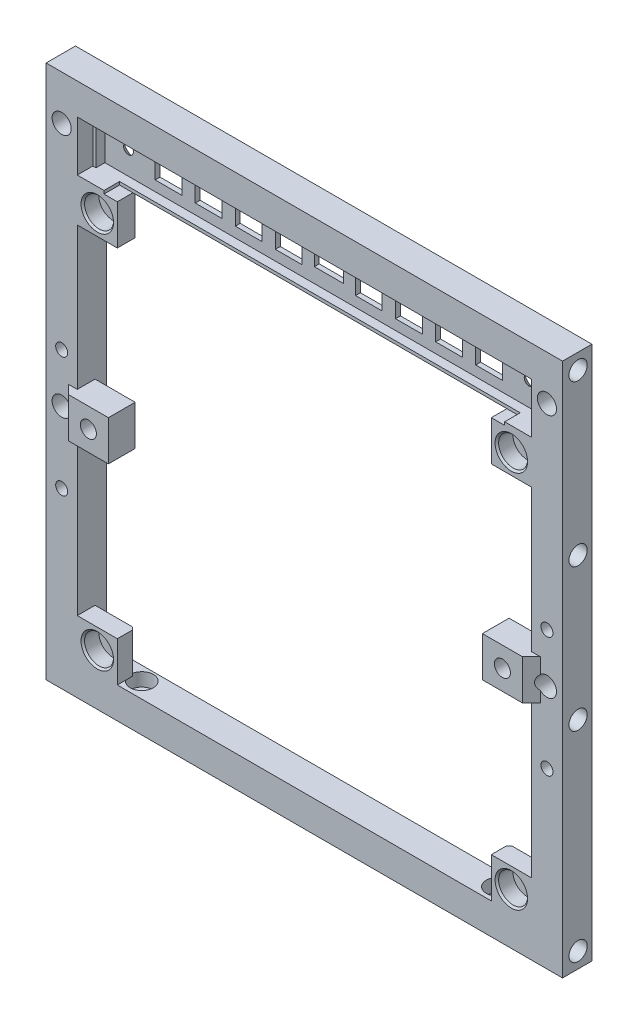
SolidWorks part; units mm, degrees
ref_plane "Front Plane" through (0, 0, 0) normal (0, 0, 1) x (1, 0, 0)
ref_plane "Top Plane" through (0, 0, 0) normal (0, 1, 0) x (1, 0, 0)
ref_plane "Right Plane" through (0, 0, 0) normal (1, 0, 0) x (0, 0, -1)
sketch "Sketch1" plane through (0, 0, 0) normal (0, 0, 1) x (1, 0, 0)
  line L1 (-58, -60) -> (58, -60)
  line L2 (-58, -60) -> (-58, 60)
  line L3 (-58, 60) -> (58, 60)
  line L4 (58, -60) -> (58, 60)
  line L5 (-58, -60) -> (58, 60) construction
  line L6 (-58, 60) -> (58, -60) construction
  line L7 (-51, -53) -> (51, -53)
  line L8 (-51, -53) -> (-51, 53)
  line L9 (-51, 53) -> (51, 53)
  line L10 (51, -53) -> (51, 53)
  line L11 (-51, -53) -> (51, 53) construction
  line L12 (-51, 53) -> (51, -53) construction
  point P0 (0, 0)
  point P6 (0, 0)
  dimension "D1" = 116
  dimension "D2" = 120
  dimension "D3" = 7
  dimension "D4" = 7
extrude "Boss-Extrude1" add sketch "Sketch1" along normal blind 7
sketch "Sketch2" plane through (-58, 0, 0) normal (-1, 0, 0) x (0, 0, 1)
  line L0 (3.5, 56.5) -> (3.5, -56.5) construction
  line L1 (7, 60) -> (0, 60) construction
  circle A0 centre (3.5, -56.5) radius 2.05
  circle A2 centre (3.5, 56.5) radius 2.05
  circle A3 centre (3.5, 20.5) radius 2.05
  circle A4 centre (3.5, -11.5) radius 2.05
  point P2 (3.5, 0)
  point P7 (3.5, 60)
  dimension "D2" = 4.1
  dimension "D3" = 36
  dimension "D4" = 45
  dimension "D1" = 3.5
extrude "Cut-Extrude1" cut sketch "Sketch2" against normal blind 6
mirror "Mirror1" about plane through (0, 0, 0) normal (1, 0, 0) of "Cut-Extrude1"
sketch "Sketch3" plane through (0, -53, 0) normal (0, 1, 0) x (1, 0, 0)
  line L0 (0, 0) -> (0, -7) construction
  line L1 (-51, 0) -> (51, 0) construction
  line L2 (-51, -7) -> (51, -7) construction
  line L3 (40, -3.5) -> (-40, -3.5) construction
  circle A0 centre (40, -3.5) radius 1.35
  circle A1 centre (-40, -3.5) radius 1.35
  point P9 (0, -3.5)
  dimension "D1" = 2.7
  dimension "D2" = 80
extrude "Cut-Extrude2" cut sketch "Sketch3" against normal through all
sketch "Sketch4" plane through (0, -53, 0) normal (0, 1, 0) x (1, 0, 0)
  circle A0 centre (40, -3.5) radius 2.6
  circle A1 centre (-40, -3.5) radius 2.6
  dimension "D1" = 5.2
extrude "Cut-Extrude3" cut sketch "Sketch4" against normal blind 3
sketch "Sketch5" plane through (0, 0, 0) normal (0, 0, -1) x (-1, 0, 0)
  line L0 (-54.5, -60) -> (-54.5, 60) construction
  line L1 (58, -60) -> (-58, -60) construction
  line L2 (-58, 60) -> (58, 60) construction
  line L3 (-51, 0) -> (-58, 0) construction
  line L4 (-51, -53) -> (-51, 53) construction
  line L5 (-58, -60) -> (-58, 60) construction
  line L6 (0, 60) -> (0, -60) construction
  line L7 (51, -53) -> (-51, -53) construction
  circle A0 centre (-54.5, 6) radius 1.35
  circle A1 centre (54.5, 6) radius 1.35
  circle A2 centre (-54.5, -21) radius 1.35
  circle A3 centre (54.5, -21) radius 1.35
  point P12 (-54.5, 0)
  point P13 (-54.5, 0)
  dimension "D1" = 2.7
  dimension "D2" = 6
  dimension "D3" = 32
extrude "Cut-Extrude4" cut sketch "Sketch5" against normal through all
sketch "Sketch6" plane through (0, 0, 0) normal (0, 0, -1) x (-1, 0, 0)
  circle A0 centre (-54.5, 6) radius 2.5
  circle A1 centre (54.5, 6) radius 2.5
  circle A2 centre (-54.5, -21) radius 2.5
  circle A3 centre (54.5, -21) radius 2.5
  dimension "D1" = 5
extrude "Cut-Extrude5" cut sketch "Sketch6" against normal blind 3
sketch "Sketch7" plane through (0, 0, 0) normal (0, 0, -1) x (-1, 0, 0)
  line L0 (-51, 53) -> (-58, 53) construction
  line L1 (-58, -60) -> (-58, 60) construction
  line L2 (-54.5, 50) -> (-54.5, -5) construction
  line L3 (-58, 60) -> (58, 60) construction
  circle A0 centre (-54.5, 50) radius 2.15
  circle A1 centre (-54.5, -5) radius 2.15
  point P8 (-54.5, 53)
  dimension "D1" = 4.3
  dimension "D2" = 10
  dimension "D3" = 55
extrude "Cut-Extrude6" cut sketch "Sketch7" against normal through all
mirror "Mirror2" about plane through (0, 0, 0) normal (1, 0, 0) of "Cut-Extrude6"
sketch "Sketch8" plane through (0, 0, 3) normal (0, 0, -1) x (-1, 0, 0)
  line L2 (-55.85, 3.8958) -> (-55.85, 8.1042)
  line L4 (-53.15, 3.8958) -> (-53.15, 8.1042)
  line L5 (-55.85, 3.8958) -> (-53.15, 8.1042) construction
  line L6 (-55.85, 8.1042) -> (-53.15, 3.8958) construction
  line L8 (-55.85, -23.1042) -> (-55.85, -18.8958)
  line L10 (-53.15, -23.1042) -> (-53.15, -18.8958)
  line L11 (-55.85, -23.1042) -> (-53.15, -18.8958) construction
  line L12 (-55.85, -18.8958) -> (-53.15, -23.1042) construction
  circle A0 centre (-54.5, 6) radius 2.5 construction
  circle A1 centre (-54.5, -21) radius 2.5 construction
  circle A2 centre (-54.5, -21) radius 2.5 construction
  arc A3 (-53.15, 8.1042) -> (-55.85, 8.1042) centre (-54.5, 6) ccw
  arc A4 (-53.15, -18.8958) -> (-55.85, -18.8958) centre (-54.5, -21) ccw
  circle A5 centre (-54.5, 6) radius 1.35 construction
  circle A6 centre (-54.5, -21) radius 1.35 construction
  arc A7 (-55.85, -23.1042) -> (-53.15, -23.1042) centre (-54.5, -21) ccw
  arc A8 (-55.85, 3.8958) -> (-53.15, 3.8958) centre (-54.5, 6) ccw
  point P0 (-54.5, 6)
  point P8 (-54.5, -21)
extrude "Cut-Extrude7" cut sketch "Sketch8" against normal blind 0.2
sketch "Sketch9" plane through (0, 0, 3.2) normal (0, 0, -1) x (-1, 0, 0)
  line L0 (-53.15, 6) -> (-53.15, 8.1042) construction
  line L1 (-55.85, 4.65) -> (-53.15, 4.65)
  line L2 (-55.85, 4.65) -> (-55.85, 7.35)
  line L3 (-55.85, 7.35) -> (-53.15, 7.35)
  line L4 (-53.15, 4.65) -> (-53.15, 7.35)
  line L5 (-55.85, 4.65) -> (-53.15, 7.35) construction
  line L6 (-55.85, 7.35) -> (-53.15, 4.65) construction
  line L7 (-53.15, -23.1042) -> (-53.15, -18.8958) construction
  line L8 (-55.85, -22.35) -> (-53.15, -22.35)
  line L9 (-55.85, -22.35) -> (-55.85, -19.65)
  line L10 (-55.85, -19.65) -> (-53.15, -19.65)
  line L11 (-53.15, -22.35) -> (-53.15, -19.65)
  line L12 (-55.85, -22.35) -> (-53.15, -19.65) construction
  line L13 (-55.85, -19.65) -> (-53.15, -22.35) construction
  arc A0 (-53.15, 6) -> (-55.85, 6) centre (-54.5, 6) ccw construction
  point P0 (-54.5, 6)
  point P8 (-54.5, -21)
extrude "Cut-Extrude8" cut sketch "Sketch9" against normal blind 0.2
mirror "Mirror3" about plane through (0, 0, 0) normal (1, 0, 0) of "Cut-Extrude8", "Cut-Extrude7"
sketch "Sketch10" plane through (0, 0, 7) normal (0, 0, 1) x (1, 0, 0)
  line L0 (51, -53) -> (51, 53) construction
  line L1 (51, -53) -> (45, -53)
  line L2 (51, -53) -> (51, -47)
  line L3 (51, -47) -> (45, -47)
  line L4 (45, -53) -> (45, -47)
  line L5 (51, -23.5) -> (45, -23.5)
  line L6 (51, -23.5) -> (51, -17.5)
  line L7 (51, -17.5) -> (45, -17.5)
  line L8 (45, -23.5) -> (45, -17.5)
  line L9 (-51, -53) -> (51, -53) construction
  dimension "D1" = 6
  dimension "D2" = 35.5
extrude "Boss-Extrude2" add sketch "Sketch10" against normal offset from surface (5.5 mm away) 1.5 up to face at (-52.35, -5, 0)
sketch "Sketch11" plane through (0, 0, 1.5) normal (0, 0, -1) x (-1, 0, 0)
  line L0 (-51, -23.5) -> (-45, -17.5) construction
  line L2 (-51, -53) -> (-45, -47) construction
  circle A0 centre (-48, -20.5) radius 1.65
  circle A1 centre (-48, -50) radius 1.65
  dimension "D1" = 3.3
extrude "Cut-Extrude9" cut sketch "Sketch11" against normal through all
mirror "Mirror4" about plane through (0, 0, 0) normal (1, 0, 0) of "Cut-Extrude9", "Boss-Extrude2"
sketch "Sketch12" plane through (0, 0, 0) normal (0, 0, -1) x (-1, 0, 0)
  line L0 (51, 53) -> (51, -53) construction
  line L1 (-51, 53) -> (51, 53)
  line L2 (-51, 53) -> (-51, 41)
  line L3 (-51, 41) -> (51, 41)
  line L4 (51, 53) -> (51, 41)
  dimension "D1" = 12
extrude "Boss-Extrude3" add sketch "Sketch12" against normal blind 1.5
sketch "Sketch13" plane through (0, 0, 1.5) normal (0, 0, 1) x (1, 0, 0)
  line L0 (-51, 53) -> (51, 41) construction
  line L2 (-50.3, 41.7) -> (50.3, 41.7)
  line L3 (-50.3, 41.7) -> (-50.3, 52.3)
  line L4 (-50.3, 52.3) -> (50.3, 52.3)
  line L5 (50.3, 41.7) -> (50.3, 52.3)
  line L6 (-50.3, 41.7) -> (50.3, 52.3) construction
  line L7 (-50.3, 52.3) -> (50.3, 41.7) construction
  line L8 (-51, 41) -> (51, 41)
  line L9 (-51, 41) -> (-51, 53)
  line L10 (-51, 53) -> (51, 53)
  line L11 (51, 41) -> (51, 53)
  line L12 (-51, 41) -> (51, 53) construction
  line L13 (-51, 53) -> (51, 41) construction
  point P4 (0, 47)
  point P9 (0, 47)
  dimension "D1" = 100.6
  dimension "D2" = 10.6
extrude "Boss-Extrude4" add sketch "Sketch13" along normal blind 2
sketch "Sketch14" plane through (0, 0, 1.5) normal (0, 0, 1) x (1, 0, 0)
  line L0 (0, 52.3) -> (0, 41.7) construction
  line L1 (50.3, 52.3) -> (-50.3, 52.3) construction
  line L2 (-50.3, 41.7) -> (50.3, 41.7) construction
  line L3 (-50.3, 47) -> (50.3, 47) construction
  line L4 (50.3, 41.7) -> (50.3, 52.3) construction
  line L5 (-33, 50) -> (-39, 50)
  line L6 (-3.25, 45) -> (3.25, 45)
  line L7 (-3.25, 45) -> (-3.25, 49)
  line L8 (-3.25, 49) -> (3.25, 49)
  line L9 (3.25, 45) -> (3.25, 49)
  line L10 (-3.25, 45) -> (3.25, 49) construction
  line L11 (-3.25, 49) -> (3.25, 45) construction
  line L12 (6, 44) -> (12, 44)
  line L13 (6, 44) -> (6, 50)
  line L14 (6, 50) -> (12, 50)
  line L15 (12, 44) -> (12, 50)
  line L16 (6, 44) -> (12, 50) construction
  line L17 (6, 50) -> (12, 44) construction
  line L18 (15, 44) -> (21, 44)
  line L19 (15, 44) -> (15, 50)
  line L20 (15, 50) -> (21, 50)
  line L21 (21, 44) -> (21, 50)
  line L22 (15, 44) -> (21, 50) construction
  line L23 (15, 50) -> (21, 44) construction
  line L24 (24, 44) -> (30, 44)
  line L25 (24, 44) -> (24, 50)
  line L26 (24, 50) -> (30, 50)
  line L27 (30, 44) -> (30, 50)
  line L28 (24, 44) -> (30, 50) construction
  line L29 (24, 50) -> (30, 44) construction
  line L30 (33, 44) -> (39, 44)
  line L31 (33, 44) -> (33, 50)
  line L32 (33, 50) -> (39, 50)
  line L33 (39, 44) -> (39, 50)
  line L34 (33, 44) -> (39, 50) construction
  line L35 (33, 50) -> (39, 44) construction
  line L36 (-39, 44) -> (-39, 50)
  line L37 (-33, 44) -> (-39, 44)
  line L38 (-33, 44) -> (-33, 50)
  line L39 (-24, 50) -> (-30, 50)
  line L40 (-30, 44) -> (-30, 50)
  line L41 (-24, 44) -> (-30, 44)
  line L42 (-24, 44) -> (-24, 50)
  line L43 (-15, 50) -> (-21, 50)
  line L44 (-21, 44) -> (-21, 50)
  line L45 (-15, 44) -> (-21, 44)
  line L46 (-15, 44) -> (-15, 50)
  line L47 (-6, 50) -> (-12, 50)
  line L48 (-12, 44) -> (-12, 50)
  line L49 (-6, 44) -> (-12, 44)
  line L50 (-6, 44) -> (-6, 50)
  circle A0 centre (-45, 47) radius 1.3 construction
  circle A1 centre (45, 47) radius 1.3 construction
  point P6 (0, 47)
  point P11 (0, 47)
  point P16 (9, 47)
  point P21 (18, 47)
  point P26 (27, 47)
  point P31 (36, 47)
  dimension "D10" = 2.6
  dimension "D9" = 45
  dimension "D1" = 6.5
  dimension "D2" = 4
  dimension "D3" = 6
  dimension "D4" = 9
  dimension "D5" = 9
  dimension "D6" = 9
  dimension "D7" = 9
  dimension "D8" = 45
extrude "Cut-Extrude10" cut sketch "Sketch14" against normal through all
sketch "Sketch15" plane through (0, 0, 1.5) normal (0, 0, 1) x (1, 0, 0)
  circle A0 centre (-45, 47) radius 1
  circle A1 centre (45, 47) radius 1
  dimension "D1" = 2
extrude "Boss-Extrude5" add sketch "Sketch15" along normal up to surface (2 mm away) up to face at (0, 47, 3.5)
chamfer "Chamfer1" distance 0.4 angle 45 4 edges at (-51, -6, 0) (51, -6, 0) (0, -53, 0) (0, 41, 0)
chamfer "Chamfer2" distance 0.4 angle 45 4 edges at (0, 60, 0) (-58, 0, 0) (0, -60, 0) (58, 0, 0)
chamfer "Chamfer3" distance 0.4 angle 45 36 edges at (-36, 44, 0) (-39, 47, 0) (-36, 50, 0) (-33, 47, 0) (-27, 44, 0) (-30, 47, 0) (-27, 50, 0) (-24, 47, 0) (-18, 44, 0) (-21, 47, 0) (-18, 50, 0) (-15, 47, 0) (-9, 44, 0) (-12, 47, 0) (-9, 50, 0) (-6, 47, 0) (0, 45, 0) (-3.25, 47, 0) (0, 49, 0) (3.25, 47, 0) (9, 44, 0) (6, 47, 0) (9, 50, 0) (12, 47, 0) (18, 44, 0) (15, 47, 0) (18, 50, 0) (21, 47, 0) (36, 44, 0) (33, 47, 0) (36, 50, 0) (39, 47, 0) (27, 44, 0) (24, 47, 0) (27, 50, 0) (30, 47, 0)
sketch "Sketch16" plane through (0, 0, 7) normal (0, 0, 1) x (1, 0, 0)
  line L0 (-45, 41) -> (-45, 41.7)
  line L1 (-51, -17.5) -> (-45, -17.5)
  line L2 (-51, -17.5) -> (-51, -11.5)
  line L3 (-51, -11.5) -> (-45, -11.5)
  line L4 (-45, -17.5) -> (-45, -11.5)
  line L5 (51, -17.5) -> (45, -17.5)
  line L6 (51, -17.5) -> (51, -11.5)
  line L7 (51, -11.5) -> (45, -11.5)
  line L8 (45, -17.5) -> (45, -11.5)
  line L9 (51, 41) -> (45, 41) construction
  line L10 (51, 41) -> (51, 35)
  line L11 (51, 35) -> (45, 35)
  line L12 (45, 41) -> (45, 35)
  line L13 (-51, 41) -> (-45, 41) construction
  line L14 (-51, 41) -> (-51, 35)
  line L15 (-51, 35) -> (-45, 35)
  line L16 (-45, 41) -> (-45, 35)
  line L17 (-50.3, 41.7) -> (50.3, 41.7) construction
  line L18 (-45, 41.7) -> (-51, 41.7)
  line L19 (-51, 53) -> (-51, 41) construction
  line L20 (-51, 41.7) -> (-51, 41)
  line L21 (45, 41) -> (45, 41.7)
  line L22 (45, 41.7) -> (51, 41.7)
  line L23 (51, 41) -> (51, 53) construction
  line L24 (51, 41.7) -> (51, 41)
  dimension "D1" = 6
extrude "Boss-Extrude7" add sketch "Sketch16" against normal offset from surface (5.5 mm away) 1.5 up to face at (-36, 47, 0)
sketch "Sketch17" plane through (0, 0, 1.5) normal (0, 0, -1) x (-1, 0, 0)
  line L0 (-45, 35) -> (45, -11.5) construction
  line L1 (-45, -11.5) -> (-45, -23.5) construction
  line L2 (-48, -14.5) -> (48, -14.5) construction
  line L3 (-48, -14.5) -> (-48, 38) construction
  line L4 (-48, 38) -> (48, 38) construction
  line L5 (48, -14.5) -> (48, 38) construction
  line L6 (-48, -14.5) -> (48, 38) construction
  line L7 (-48, 38) -> (48, -14.5) construction
  line L8 (45, -11.5) -> (51, -11.5) construction
  circle A0 centre (-48, -14.5) radius 1.65
  circle A1 centre (48, -14.5) radius 1.65
  circle A2 centre (48, 38) radius 1.65
  circle A3 centre (-48, 38) radius 1.65
  point P4 (0, 11.75)
  dimension "D3" = 3.3
  dimension "D1" = 3
  dimension "D2" = 3
extrude "Cut-Extrude11" cut sketch "Sketch17" against normal through all
sketch "Sketch18" plane through (0, 0, 1.5) normal (0, 0, 1) x (1, 0, 0)
  circle A0 centre (-45, 47) radius 1.1
  circle A1 centre (45, 47) radius 1.1
  dimension "D1" = 2.2
extrude "Cut-Extrude12" cut sketch "Sketch18" against normal through all both and the other way through all
chamfer "Chamfer4" distance 1.5 angle 45 2 edges at (-43.9, 47, 0) (46.1, 47, 0)
sketch "Sketch19" plane through (0, 0, 1.5) normal (0, 0, -1) x (-1, 0, 0)
  line L1 (-51, -53) -> (51, -53)
  line L2 (-51, -53) -> (-51, 41)
  line L3 (-51, 41) -> (51, 41)
  line L4 (51, -53) -> (51, 41)
extrude "Cut-Extrude13" cut sketch "Sketch19" against normal through all
ref_plane "Plane1" through (0, 0, 3) normal (0, 0, -1) x (-1, 0, 0)
sketch "Sketch20" plane through (0, 0, 3) normal (0, 0, -1) x (-1, 0, 0)
  line L0 (0, 41.4) -> (0, -53.4) construction
  line L1 (-51, 41) -> (-43, 41)
  line L2 (-51, 41) -> (-51, 33)
  line L3 (-51, 33) -> (-43, 33)
  line L4 (-43, 41) -> (-43, 33)
  line L5 (-51, -53) -> (-43, -53)
  line L6 (-51, -53) -> (-51, -45)
  line L7 (-51, -45) -> (-43, -45)
  line L8 (-43, -53) -> (-43, -45)
  line L9 (-51.4, 41.4) -> (51.4, 41.4) construction
  line L10 (51.4, -53.4) -> (-51.4, -53.4) construction
  line L11 (43, -53) -> (43, -45)
  line L12 (51, -45) -> (43, -45)
  line L13 (51, -53) -> (51, -45)
  line L14 (51, -53) -> (43, -53)
  line L15 (43, 41) -> (43, 33)
  line L16 (51, 33) -> (43, 33)
  line L17 (51, 41) -> (51, 33)
  line L18 (51, 41) -> (43, 41)
  dimension "D1" = 8
extrude "Boss-Extrude8" add sketch "Sketch20" against normal blind 7
sketch "Sketch21" plane through (0, 0, 3) normal (0, 0, -1) x (-1, 0, 0)
  line L0 (-51, 33) -> (-43, 41) construction
  line L1 (-51, -45) -> (-43, -53) construction
  line L2 (0, 0) -> (0, 50000) construction
  line L3 (51, -45) -> (43, -53) construction
  line L4 (51, 33) -> (43, 41) construction
  circle A0 centre (-47, 37) radius 2.15
  circle A1 centre (-47, -49) radius 2.15
  circle A2 centre (47, -49) radius 2.15
  circle A3 centre (47, 37) radius 2.15
  dimension "D1" = 4.3
extrude "Cut-Extrude14" cut sketch "Sketch21" against normal through all
chamfer "Chamfer6" distance 0.4 angle 45 4 edges at (44.85, -49, 3) (-44.85, -49, 3) (-44.85, 37, 3) (44.85, 37, 3)
chamfer "Chamfer7" distance 0.4 angle 45 4 edges at (-52.35, 50, 0) (-52.35, -5, 0) (52.35, -5, 0) (52.35, 50, 0)
sketch "Sketch22" plane through (0, 0, 3) normal (0, 0, -1) x (-1, 0, 0)
  line L1 (-51, -53) -> (51, -53)
  line L2 (-51, -53) -> (-51, 41)
  line L3 (-51, 41) -> (51, 41)
  line L4 (51, -53) -> (51, 41)
extrude "Cut-Extrude15" cut sketch "Sketch22" against normal through all
ref_plane "Plane2" through (0, 0, 3) normal (0, 0, -1) x (-1, 0, 0)
sketch "Sketch24" plane through (0, 0, 3) normal (0, 0, -1) x (-1, 0, 0)
  line L0 (0, 41.4) -> (0, -53) construction
  line L1 (-51, 41) -> (-42, 41)
  line L2 (-51, 41) -> (-51, 32)
  line L3 (-51, 32) -> (-42, 32)
  line L4 (-42, 41) -> (-42, 32)
  line L5 (-51, -53) -> (-42, -53)
  line L6 (-51, -53) -> (-51, -44)
  line L7 (-51, -44) -> (-42, -44)
  line L8 (-42, -53) -> (-42, -44)
  line L9 (-51.4, 41.4) -> (51.4, 41.4) construction
  line L10 (-51, -53) -> (51, -53) construction
  dimension "D1" = 9
extrude "Boss-Extrude9" add sketch "Sketch24" against normal up to surface (4 mm away) up to face at (0, 27.5667, 7)
sketch "Sketch25" plane through (0, 0, 7) normal (0, 0, 1) x (1, 0, 0)
  line L0 (42, 41) -> (51, 32) construction
  line L1 (42, -44) -> (51, -53) construction
  circle A0 centre (46.5, 36.5) radius 3.25
  circle A1 centre (46.5, -48.5) radius 3.25
  dimension "D1" = 6.5
extrude "Cut-Extrude16" cut sketch "Sketch25" against normal offset from surface (3.6 mm away) 0.4 up to face at (46.5, 36.5, 3)
chamfer "Chamfer8" distance 0.4 angle 45 2 edges at (49.75, -48.5, 7) (49.75, 36.5, 7)
chamfer "Chamfer9" distance 0.6 angle 45 1 edges at (42, -48.5, 3)
mirror "Mirror5" about plane through (0, 0, 0) normal (1, 0, 0) of "Chamfer9", "Chamfer8", "Cut-Extrude16", "Boss-Extrude9"
sketch "Sketch26" plane through (0, 0, 3) normal (0, 0, -1) x (-1, 0, 0)
  line L0 (-51, 41) -> (-51, -53) construction
  line L1 (-51, 0) -> (-42, 0)
  line L2 (-51, 0) -> (-51, -9)
  line L3 (-51, -9) -> (-42, -9)
  line L4 (-42, 0) -> (-42, -9)
  line L5 (-42, 32) -> (-42, 41) construction
  line L6 (-51, 32) -> (-42, 32) construction
  dimension "D1" = 32
extrude "Boss-Extrude10" add sketch "Sketch26" against normal blind 6
sketch "Sketch27" plane through (0, 0, 3) normal (0, 0, -1) x (-1, 0, 0)
  line L0 (-42, 0) -> (-51, -9) construction
  circle A0 centre (-46.5, -4.5) radius 1.8
  dimension "D1" = 3.6
extrude "Cut-Extrude17" cut sketch "Sketch27" against normal through all
chamfer "Chamfer10" distance 2 angle 45 1 edges at (51, -4.5, 7)
mirror "Mirror6" about plane through (0, 0, 0) normal (1, 0, 0) of "Cut-Extrude17", "Chamfer10", "Boss-Extrude10"
